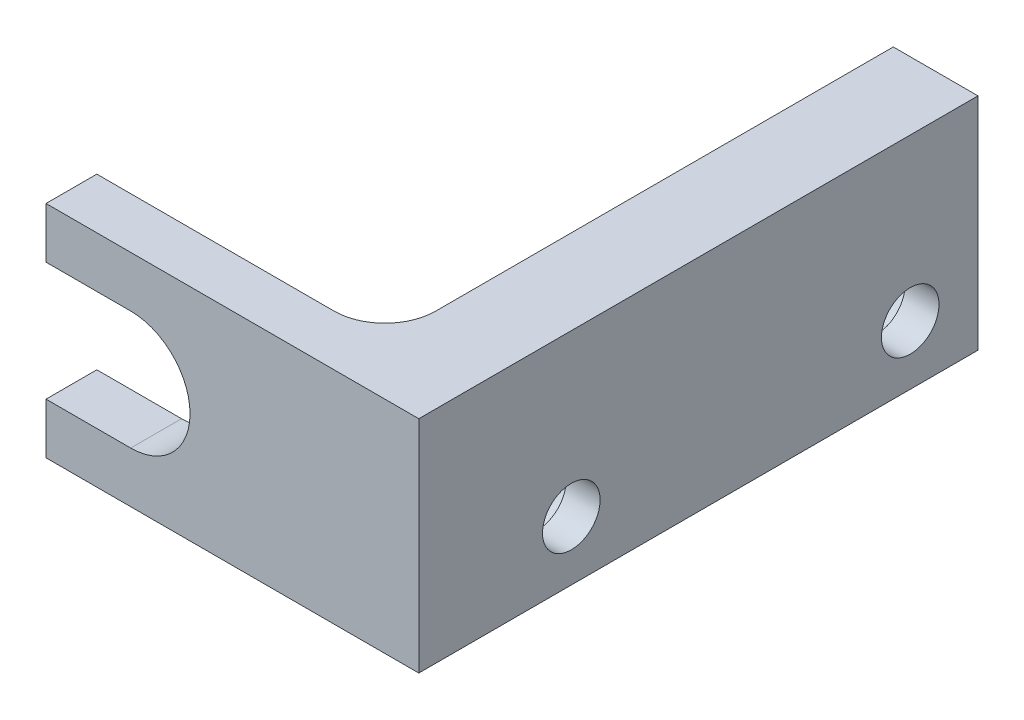
SolidWorks part; units mm, degrees
material "45#"
ref_plane "前视" through (0, 0, 0) normal (0, 0, 1) x (1, 0, 0)
ref_plane "上视" through (0, 0, 0) normal (0, 1, 0) x (1, 0, 0)
ref_plane "右视" through (0, 0, 0) normal (1, 0, 0) x (0, 0, -1)
sketch "草图1" plane through (0, 0, 0) normal (0, 0, 1) x (1, 0, 0)
  line L1 (-11, -6.5) -> (11, -6.5)
  line L2 (-11, -6.5) -> (-11, 6.5)
  line L3 (-11, 6.5) -> (11, 6.5)
  line L4 (11, -6.5) -> (11, 6.5)
  line L5 (-11, -6.5) -> (11, 6.5) construction
  line L6 (-11, 6.5) -> (11, -6.5) construction
  point P0 (0, 0)
  dimension "D1" = 22
  dimension "D2" = 13
extrude "凸台-拉伸1" add sketch "草图1" along normal blind 33
sketch "草图5" plane through (-11, 0, 0) normal (-1, 0, 0) x (0, 0, 1)
  line L0 (0, 6.5) -> (0, -6.5) construction
  line L1 (33, 6.5) -> (33, -6.5) construction
  line L3 (33, 6.5) -> (0, 6.5) construction
  line L8 (0, 6.5) -> (30, 6.5)
  line L11 (0, 6.5) -> (0, -6.5)
  line L12 (0, -6.5) -> (30, -6.5)
  line L13 (30, 6.5) -> (30, -6.5)
  dimension "D1" = 3
extrude "切除-拉伸2" cut sketch "草图5" against normal offset from surface (17 mm away) 5 up to face at (11, 0, 16.5)
hole_wizard "打孔尺寸根据内六角圆柱头螺钉的类型1" positions "草图11" profile "草图10" counterbore size "M3" standard "Gb" end condition through all
sketch "草图11" plane through (6, 5.5329, -4.0596) normal (-1, 0, 0) x (0, 0, 1)
  line L0 (-4, -8.5329) -> (8.5055, -8.5329) construction
  line L4 (34.0596, -12.0329) -> (4.0596, -12.0329) construction
  line L5 (4.0596, -12.0329) -> (4.0596, 0.9671) construction
  point P0 (28.0596, -8.5329)
  point P7 (8.0596, -8.5329)
  dimension "D1" = 4
  dimension "D2" = 20
  dimension "D3" = 3.5
sketch "草图10" plane through (6, -3, 24) normal (0, 1, 0) x (0, 0, 1)
  line L0 (0, 0) -> (0, 5)
  line L1 (0, 5) -> (1.7, 5)
  line L3 (1.7, 5) -> (1.7, 3)
  line L4 (1.7, 3) -> (3, 3)
  line L5 (3, 3) -> (3, 0)
  line L7 (3, 0) -> (0, 0)
  line L11 (0, -6.35) -> (0, 107.95) construction
  dimension "通孔孔直径" = 3.4
  dimension "通孔孔深度" = 5
  dimension "柱形沉头孔直径" = 6
  dimension "柱形沉头孔深度" = 3
sketch "草图12" plane through (0, 0, 33) normal (0, 0, 1) x (1, 0, 0)
  line L2 (-11, 0) -> (5.3566, 0) construction
  line L3 (-11, 6.5) -> (-11, -6.5) construction
  line L4 (11, -6.5) -> (11, 6.5) construction
  line L5 (-11, -3.5) -> (-6, -3.5)
  line L6 (-11, -3.5) -> (-11, 3.5)
  line L7 (-11, 3.5) -> (-6, 3.5)
  line L9 (-11, -3.5) -> (-6, 3.5) construction
  line L10 (-11, 3.5) -> (-6, -3.5) construction
  arc A0 (-6, 3.5) -> (-6, -3.5) centre (-6, 0) cw
  point P4 (-8.5, 0)
  dimension "D1" = 7
  dimension "D2" = 17
extrude "切除-拉伸4" cut sketch "草图12" against normal through all
fillet "圆角1" radius 3 1 edges at (6, 0, 30)
